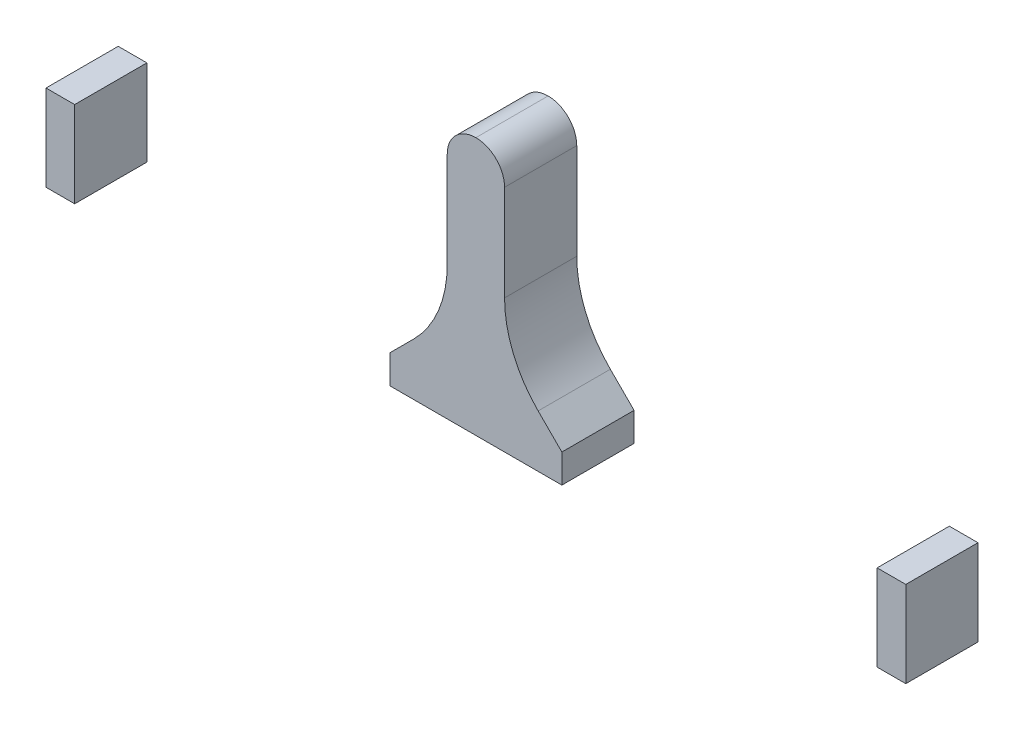
SolidWorks part; units mm, degrees
ref_plane "Front Plane" through (0, 0, 0) normal (0, 0, 1) x (1, 0, 0)
ref_plane "Top Plane" through (0, 0, 0) normal (0, 1, 0) x (1, 0, 0)
ref_plane "Right Plane" through (0, 0, 0) normal (1, 0, 0) x (0, 0, -1)
sketch "Sketch1" plane through (0, 0, 0) normal (0, 0, 1) x (1, 0, 0)
  line L0 (-3.175, 0) -> (-3.175, 19.05)
  line L1 (-3.175, 19.05) -> (3.175, 19.05)
  line L2 (3.175, 19.05) -> (3.175, 0)
  line L3 (-3.175, 0) -> (-9.525, -6.35)
  line L4 (-9.525, -6.35) -> (9.525, -6.35) construction
  line L5 (9.525, -6.35) -> (3.175, 0)
  line L6 (-9.525, -6.35) -> (-9.525, -9.525)
  line L7 (-9.525, -9.525) -> (9.525, -9.525)
  line L8 (9.525, -9.525) -> (9.525, -6.35)
  line L9 (-44.45, -9.525) -> (-44.45, 0)
  line L10 (-44.45, 0) -> (-47.625, 0)
  line L11 (-47.625, 0) -> (-47.625, -9.525)
  line L12 (-47.625, -9.525) -> (-44.45, -9.525)
  line L13 (-46.0375, 0) -> (0, 19.05) construction
  line L14 (0, 19.05) -> (0, 0) construction
  line L15 (0, 0) -> (-46.0375, 0) construction
  line L16 (47.625, -9.525) -> (44.45, -9.525)
  line L17 (47.625, 0) -> (47.625, -9.525)
  line L18 (44.45, 0) -> (47.625, 0)
  line L19 (44.45, -9.525) -> (44.45, 0)
  point P4 (0, 19.05)
  dimension "D1" = 6.35
  dimension "D2" = 19.05
  dimension "D3" = 19.05
  dimension "D4" = 6.35
  dimension "D5" = 3.175
  dimension "D6" = 3.175
  dimension "D7" = 34.925
  dimension "D8" = 19.05
extrude "Boss-Extrude1" add sketch "Sketch1" along normal mid plane 8
fillet "Fillet1" radius 3.175 2 edges at (-3.175, 19.05, 0) (3.175, 19.05, 0)
fillet "Fillet2" radius 12.7 2 edges at (3.175, 0, 0) (-3.175, 0, 0)
sketch "Sketch2" plane through (0, 0, -4) normal (0, 0, 1) x (1, 0, 0)
  line L0 (0, 19.05) -> (0, -9.525) construction
  line L1 (-9.525, -9.525) -> (9.525, -9.525) construction
